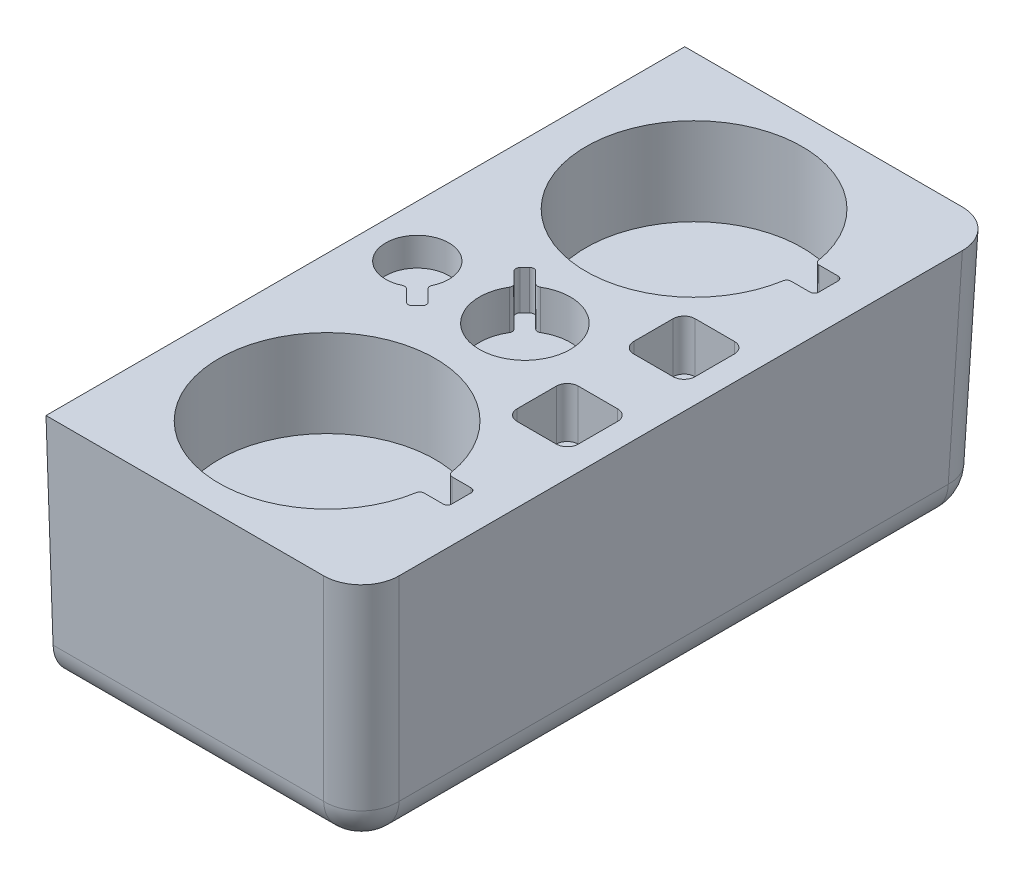
SolidWorks part; units mm, degrees
ref_plane "Front Plane" through (0, 0, 0) normal (0, 0, 1) x (1, 0, 0)
ref_plane "Top Plane" through (0, 0, 0) normal (0, 1, 0) x (1, 0, 0)
ref_plane "Right Plane" through (0, 0, 0) normal (1, 0, 0) x (0, 0, -1)
sketch "Sketch3" plane through (0, 0, 0) normal (0, 1, 0) x (1, 0, 0)
  line L1 (-70.2, -142.24) -> (70.2, -142.24)
  line L2 (-70.2, -142.24) -> (-70.2, 142.24)
  line L3 (-70.2, 142.24) -> (70.2, 142.24)
  line L4 (70.2, -142.24) -> (70.2, 142.24)
  line L5 (-70.2, -142.24) -> (70.2, 142.24) construction
  line L6 (-70.2, 142.24) -> (70.2, -142.24) construction
  point P0 (0, 0)
  dimension "D1" = 140.4
  dimension "D2" = 284.48
extrude "Boss-Extrude1" add sketch "Sketch3" along normal blind 109.22 draft 2 draft outward yes
sketch "Sketch1" plane through (0, 0, 0) normal (0, 1, 0) x (1, 0, 0)
  line L0 (45.236, 90.304) -> (57.636, 90.304)
  line L5 (57.636, 90.304) -> (57.636, 77.504)
  line L6 (57.636, 77.504) -> (45.236, 77.504)
  line L7 (45.236, -77.504) -> (57.636, -77.504)
  line L8 (57.636, -77.504) -> (57.636, -90.304)
  line L9 (57.636, -90.304) -> (45.236, -90.304)
  line L16 (39.838, 12.7) -> (57.838, 12.7)
  line L17 (34.838, 17.7) -> (34.838, 35.7)
  line L18 (39.838, 40.7) -> (57.838, 40.7)
  line L19 (62.838, 17.7) -> (62.838, 35.7)
  line L20 (34.838, 12.7) -> (62.838, 40.7) construction
  line L21 (34.838, 40.7) -> (62.838, 12.7) construction
  line L22 (39.838, -40.7) -> (57.838, -40.7)
  line L23 (34.838, -35.7) -> (34.838, -17.7)
  line L24 (39.838, -12.7) -> (57.838, -12.7)
  line L25 (62.838, -35.7) -> (62.838, -17.7)
  line L26 (34.838, -40.7) -> (62.838, -12.7) construction
  line L27 (34.838, -12.7) -> (62.838, -40.7) construction
  line L28 (-72.9829, 0) -> (78.453, 0) construction
  line L29 (74.014, 146.054) -> (-74.014, 146.054) construction
  line L31 (-74.014, 146.054) -> (-74.014, -146.054) construction
  line L34 (74.014, -146.054) -> (74.014, 146.054) construction
  line L35 (-74.014, -146.054) -> (74.014, -146.054) construction
  line L42 (-16.8542, 24.539) -> (-9.2882, 16.973)
  line L43 (-16.8542, 24.539) -> (-21.804, 19.5893)
  line L44 (-21.804, 19.5893) -> (-14.2379, 12.0232)
  line L45 (-19.3291, 22.0641) -> (2.735, 0) construction
  line L46 (-46.4604, 0) -> (-28.7687, -17.6916) construction
  line L47 (-39.0218, -12.3883) -> (-31.2436, -20.1665)
  line L48 (-31.2436, -20.1665) -> (-26.2939, -15.2167)
  line L49 (-26.2939, -15.2167) -> (-34.072, -7.4386)
  arc A0 (45.236, 90.304) -> (45.236, 77.504) centre (-3.798, 83.904) ccw
  arc A1 (45.236, -77.504) -> (45.236, -90.304) centre (-3.798, -83.904) ccw
  arc A4 (57.838, 40.7) -> (62.838, 35.7) centre (57.838, 35.7) cw
  arc A5 (57.838, 12.7) -> (62.838, 17.7) centre (57.838, 17.7) ccw
  arc A6 (39.838, 12.7) -> (34.838, 17.7) centre (39.838, 17.7) cw
  arc A7 (34.838, 35.7) -> (39.838, 40.7) centre (39.838, 35.7) cw
  arc A8 (39.838, -40.7) -> (34.838, -35.7) centre (39.838, -35.7) cw
  arc A9 (57.838, -40.7) -> (62.838, -35.7) centre (57.838, -35.7) ccw
  arc A10 (57.838, -12.7) -> (62.838, -17.7) centre (57.838, -17.7) cw
  arc A11 (34.838, -17.7) -> (39.838, -12.7) centre (39.838, -17.7) cw
  arc A12 (-34.072, -7.4386) -> (-39.0218, -12.3883) centre (-46.4604, 0) ccw
  arc A16 (-14.2379, 12.0232) -> (-9.2882, 16.973) centre (2.735, 0) ccw
  circle A17 centre (48.838, 26.7) radius 8.35
  circle A18 centre (48.838, -26.7) radius 8.35
  point P13 (48.838, 12.7)
  point P25 (48.838, 26.7)
  point P42 (48.838, -26.7)
  dimension "D3" = 98.9
  dimension "D4" = 98.9
  dimension "D8" = 20.8
  dimension "D11" = 11.303
  dimension "D15" = 5
  dimension "D18" = 5
  dimension "D5" = 12.7
  dimension "D19" = 77.8121
  dimension "D20" = 12.7
  dimension "D21" = 28.9
  dimension "D22" = 135
  dimension "D23" = 7
  dimension "D25" = 12.7
  dimension "D12" = 13.1037
  dimension "D13" = 45
  dimension "D27" = 16.7
  dimension "D1" = 12.4
  dimension "D2" = 12.8
  dimension "D6" = 12.8
  dimension "D7" = 12.4
  dimension "D9" = 7
  dimension "D10" = 10.7
  dimension "D14" = 28
  dimension "D16" = 28
  dimension "D17" = 28
  dimension "D24" = 11
  dimension "D26" = 11.176
fillet "Fillet1" radius 17.272 5 edges at (0, 0, -142.24) (0, 0, 142.24) (70.2, 0, 0) (72.107, 54.61, -144.147) (72.107, 54.61, 144.147)
extrude "Cut-Extrude1" cut sketch "Sketch1" against normal blind 40 from surface contours A0 L6 L5 L0 | A1 L9 L8 L7 starting at face at (20.1096, 109.22, 0)
extrude "Cut-Extrude2" cut sketch "Sketch1<4>" against normal blind 13 from surface contours L49 A12 L47 L48 region at (-45.034, 0, 1.4263) starting at face at (26.815, 109.22, 83.904)
sketch "Sketch1<4>" plane through (0, 0, 0) normal (0, 1, 0) x (1, 0, 0) same geometry as "Sketch1"
extrude "Cut-Extrude3" cut sketch "Sketch1<5>" against normal blind 18 from surface contours L44 A16 L42 L43 region at (1.7934, 0, -0.9416) starting at face at (-37.6906, 109.22, 8.7697)
sketch "Sketch1<5>" plane through (0, 0, 0) normal (0, 1, 0) x (1, 0, 0) same geometry as "Sketch1"
extrude "Cut-Extrude5" cut sketch "Sketch1<6>" against normal blind 23 from surface contours A7 L17 A6 L16 A5 L19 A4 L18 | A11 L23 A8 L22 A9 L25 A10 L24 region at (36.5825, 0, -14.4445) region at (36.5825, 0, 38.9555) starting at face at (-8.2446, 109.22, -10.9796)
sketch "Sketch1<6>" plane through (0, 0, 0) normal (0, 1, 0) x (1, 0, 0) same geometry as "Sketch1"
extrude "Cut-Extrude7" cut sketch "Sketch1<7>" against normal blind 31 from surface contours A17 | A18 region at (48.838, 0, -26.7) region at (48.838, 0, 26.7) starting at face at (48.838, 109.22, 26.7)
sketch "Sketch1<7>" plane through (0, 0, 0) normal (0, 1, 0) x (1, 0, 0) same geometry as "Sketch1"
fillet "Fillet2" radius 2 16 edges at (45.236, 89.22, 90.304) (45.236, 89.22, 77.504) (57.636, 89.22, 77.504) (57.636, 89.22, 90.304) (-31.2436, 102.72, 20.1665) (-26.2939, 102.72, 15.2167) (-34.072, 102.72, 7.4386) (-39.0218, 102.72, 12.3883) (-14.2379, 100.22, -12.0232) (-21.804, 100.22, -19.5893) (-16.8542, 100.22, -24.539) (-9.2882, 100.22, -16.973) (45.236, 89.22, -77.504) (57.636, 89.22, -90.304) (57.636, 89.22, -77.504) (45.236, 89.22, -90.304)
sketch "Sketch4" plane through (0, 0, 0) normal (0, 0, 1) x (1, 0, 0)
  line L1 (-74.014, 109.22) -> (56.7526, 109.22) construction
  line L2 (-70.2, 109.22) -> (-70.2, 0)
  line L3 (-70.2, 0) -> (-85.4637, 109.22)
  line L4 (-85.4637, 109.22) -> (-70.2, 109.22)
  dimension "D2" = 110.2814
extrude "Cut-Extrude8" cut sketch "Sketch4" against normal through all both and the other way through all contours L3 L4 L2
